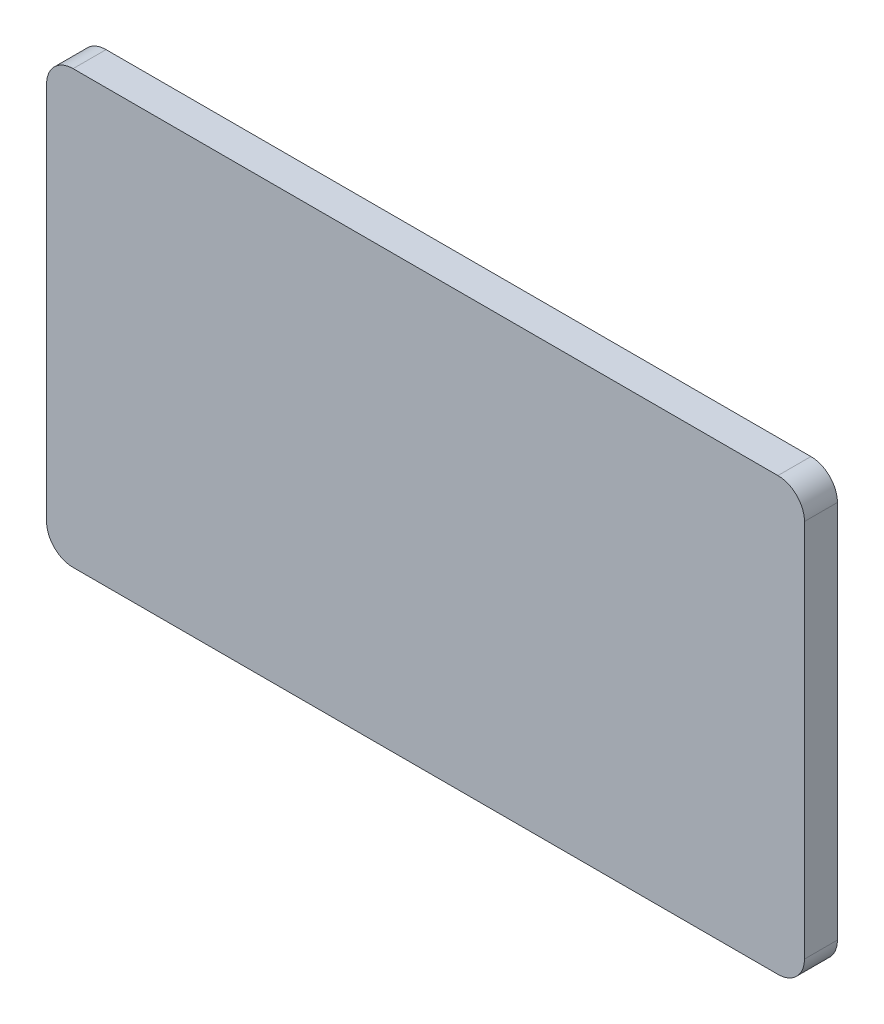
SolidWorks part; units mm, degrees
ref_plane "Front Plane" through (0, 0, 0) normal (0, 0, 1) x (1, 0, 0)
ref_plane "Top Plane" through (0, 0, 0) normal (0, 1, 0) x (1, 0, 0)
ref_plane "Right Plane" through (0, 0, 0) normal (1, 0, 0) x (0, 0, -1)
sketch "Sketch1" plane through (0, 0, 0) normal (0, 0, 1) x (1, 0, 0)
  line L1 (-100, 0) -> (100, 0)
  line L2 (-100, 0) -> (-100, 114)
  line L3 (-100, 114) -> (100, 114)
  line L4 (100, 0) -> (100, 114)
  line L5 (-75.5, 104) -> (75.5, 104)
  line L6 (-75.5, 104) -> (-75.5, 10)
  line L7 (-75.5, 10) -> (75.5, 10)
  line L8 (75.5, 104) -> (75.5, 10)
  point P10 (-75.5, 57)
  point P11 (-100, 57)
  point P12 (0, 104)
  point P13 (0, 114)
  dimension "D1" = 200
  dimension "D2" = 114
  dimension "D3" = 151
  dimension "D4" = 94
  dimension "D6" = 10
  dimension "D7" = 10
extrude "Boss-Extrude1" add sketch "Sketch1" along normal blind 8.7 contours L3 L4 L1 L2
extrude "Cut-Extrude1" cut sketch "Sketch1<3>" along normal blind 2 contours L6 L7 L8 L5
sketch "Sketch1<3>" plane through (0, 0, 0) normal (0, 0, 1) x (1, 0, 0) same geometry as "Sketch1"
fillet "Fillet1" radius 7 4 edges at (100, 114, 4.35) (100, 0, 4.35) (-100, 114, 4.35) (-100, 0, 4.35)
